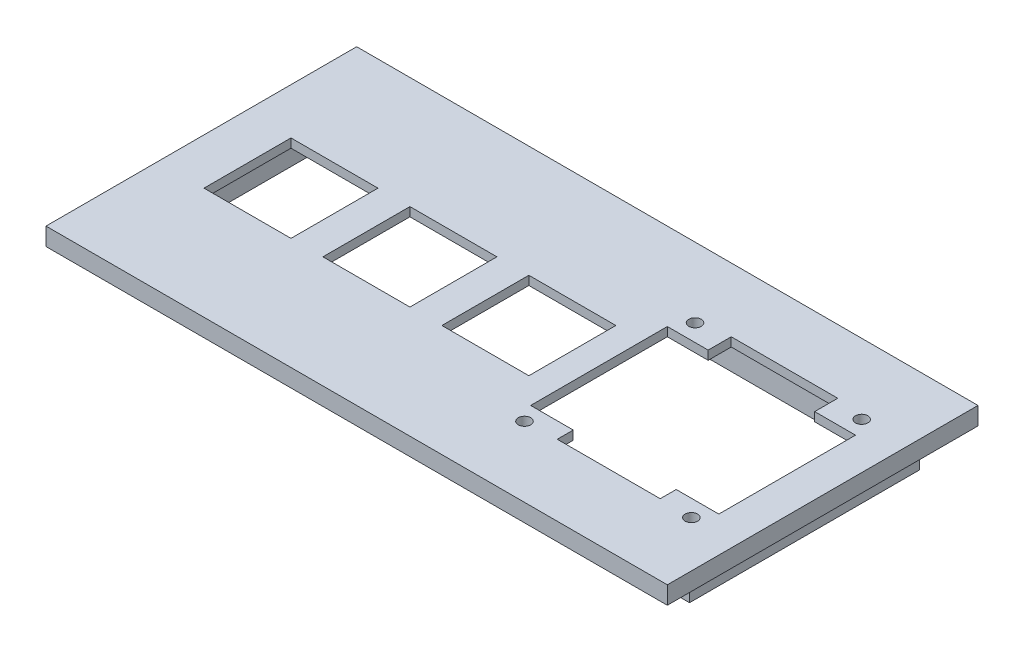
SolidWorks part; units mm, degrees
ref_plane "Front Plane" through (0, 0, 0) normal (0, 0, 1) x (1, 0, 0)
ref_plane "Top Plane" through (0, 0, 0) normal (0, 1, 0) x (1, 0, 0)
ref_plane "Right Plane" through (0, 0, 0) normal (1, 0, 0) x (0, 0, -1)
sketch "Sketch2" plane through (0, 0, 0) normal (0, 1, 0) x (1, 0, 0)
  line L1 (44.45, -22.225) -> (-44.45, -22.225)
  line L2 (44.45, -22.225) -> (44.45, 22.225)
  line L3 (44.45, 22.225) -> (-44.45, 22.225)
  line L4 (-44.45, -22.225) -> (-44.45, 22.225)
  line L5 (44.45, -22.225) -> (-44.45, 22.225) construction
  line L6 (44.45, 22.225) -> (-44.45, -22.225) construction
  point P0 (0, 0)
  dimension "D1" = 44.45
  dimension "D2" = 88.9
extrude "Boss-Extrude1" add sketch "Sketch2" along normal blind 2.54
sketch "Sketch5" plane through (0, 0, 0) normal (0, -1, 0) x (1, 0, 0)
  line L1 (41.91, -16.383) -> (-41.91, -16.383)
  line L2 (41.91, -16.383) -> (41.91, 16.51)
  line L3 (41.91, 16.51) -> (-41.91, 16.51)
  line L4 (-41.91, -16.383) -> (-41.91, 16.51)
  line L6 (-44.45, -22.225) -> (-44.45, 22.225) construction
  line L7 (44.45, 22.225) -> (44.45, -22.225) construction
  line L8 (-44.45, 22.225) -> (44.45, 22.225) construction
  line L9 (44.45, -22.225) -> (-44.45, -22.225) construction
  point P0 (0, 0)
  dimension "D1" = 2.54
  dimension "D2" = 2.54
  dimension "D3" = 5.715
  dimension "D4" = 5.842
extrude "Boss-Extrude2" add sketch "Sketch5" along normal blind 3.81
shell "Shell1" thickness 1.27 removed face at (0, -3.81, 0.0635)
sketch "Sketch3" plane through (0, 2.54, 0) normal (0, 1, 0) x (1, 0, 0)
  line L0 (-53.6471, 0) -> (105.4631, 0) construction
  line L1 (39.497, -13.868) -> (12.319, -13.868) construction
  line L2 (39.497, -13.868) -> (39.497, 13.868) construction
  line L3 (39.497, 13.868) -> (12.319, 13.868) construction
  line L4 (12.319, -13.868) -> (12.319, 13.868) construction
  line L5 (39.497, -13.868) -> (12.319, 13.868) construction
  line L6 (39.497, 13.868) -> (12.319, -13.868) construction
  line L7 (44.45, -22.225) -> (44.45, 22.225) construction
  line L8 (39.37, -9.779) -> (12.446, -9.779)
  line L9 (39.37, -9.779) -> (39.37, 9.779)
  line L10 (39.37, 9.779) -> (12.446, 9.779)
  line L11 (12.446, -9.779) -> (12.446, 9.779)
  line L12 (39.37, -9.779) -> (12.446, 9.779) construction
  line L13 (39.37, 9.779) -> (12.446, -9.779) construction
  circle A0 centre (37.846, 12.1831) radius 0.889
  circle A1 centre (13.97, 12.217) radius 0.889
  circle A2 centre (13.97, -12.1831) radius 0.889
  circle A3 centre (37.846, -12.1831) radius 0.889
  point P0 (25.908, 0)
  point P17 (25.908, 0)
  dimension "D3" = 1.778
  dimension "D4" = 1.651
  dimension "D5" = 1.651
  dimension "D6" = 1.651
  dimension "D7" = 1.6849
  dimension "D8" = 1.651
  dimension "D9" = 1.651
  dimension "D1" = 27.736
  dimension "D2" = 27.178
  dimension "D10" = 19.558
  dimension "D11" = 26.924
  dimension "D12" = 5.08
extrude "Cut-Extrude1" cut sketch "Sketch3" against normal through all both and the other way through all contours L11 L8 L9 L10 region at (25.908, 2.54, 0)
sketch "Sketch4" plane through (0, 2.54, 0) normal (0, 1, 0) x (1, 0, 0)
  line L0 (-53.9332, 0) -> (57.1003, 0) construction
  line L1 (-6.604, 21.7261) -> (-6.604, -24.0188) construction
  line L2 (8.636, -6.223) -> (-3.81, -6.223)
  line L3 (8.636, -6.223) -> (8.636, 6.223)
  line L4 (8.636, 6.223) -> (-3.81, 6.223)
  line L5 (-3.81, -6.223) -> (-3.81, 6.223)
  line L6 (8.636, -6.223) -> (-3.81, 6.223) construction
  line L7 (8.636, 6.223) -> (-3.81, -6.223) construction
  line L8 (-24.384, 21.7261) -> (-24.384, -27.2655) construction
  line L9 (12.446, 9.779) -> (12.446, -9.779) construction
  line L11 (-8.382, -6.223) -> (-20.828, -6.223)
  line L12 (-8.382, -6.223) -> (-8.382, 6.223)
  line L13 (-8.382, 6.223) -> (-20.828, 6.223)
  line L14 (-20.828, -6.223) -> (-20.828, 6.223)
  line L15 (-8.382, -6.223) -> (-20.828, 6.223) construction
  line L16 (-8.382, 6.223) -> (-20.828, -6.223) construction
  line L17 (-25.4, -6.223) -> (-37.846, -6.223)
  line L18 (-25.4, -6.223) -> (-25.4, 6.223)
  line L19 (-25.4, 6.223) -> (-37.846, 6.223)
  line L20 (-37.846, -6.223) -> (-37.846, 6.223)
  line L21 (-25.4, -6.223) -> (-37.846, 6.223) construction
  line L22 (-25.4, 6.223) -> (-37.846, -6.223) construction
  line L23 (-45.5544, -6.223) -> (13.3654, -6.223) construction
  point P3 (2.413, 0)
  point P14 (-14.605, 0)
  point P19 (-31.623, 0)
  dimension "D1" = 12.446
  dimension "D2" = 12.446
  dimension "D3" = 19.05
  dimension "D4" = 17.78
  dimension "D5" = 3.81
  dimension "D6" = 12.446
  dimension "D7" = 12.446
  dimension "D8" = 4.572
  dimension "D9" = 3.556
  dimension "D10" = 4.572
  dimension "D11" = 12.446
  dimension "D12" = 12.446
extrude "Cut-Extrude2" cut sketch "Sketch4" against normal through all both and the other way through all
extrude "Cut-Extrude3" cut sketch "Sketch3<3>" against normal blind 2.54 and the other way through all contours A3 | A2 | A1 | A0 region at (37.846, 2.54, -12.1831) region at (13.97, 2.54, -12.217) region at (13.97, 2.54, 12.1831) region at (37.846, 2.54, 12.1831)
sketch "Sketch3<3>" plane through (0, 2.54, 0) normal (0, 1, 0) x (1, 0, 0) same geometry as "Sketch3"
sketch "Sketch6" plane through (0, 2.54, 0) normal (0, 1, 0) x (1, 0, 0)
  line L0 (13.97, -12.1831) -> (37.846, -12.1831) construction
  line L1 (39.37, -9.779) -> (12.446, -9.779) construction
  line L2 (33.274, -12.065) -> (18.542, -12.065)
  line L3 (33.274, -12.065) -> (33.274, -9.779)
  line L4 (33.274, -9.779) -> (18.542, -9.779)
  line L5 (18.542, -12.065) -> (18.542, -9.779)
  line L6 (33.274, -12.065) -> (18.542, -9.779) construction
  line L7 (33.274, -9.779) -> (18.542, -12.065) construction
  line L8 (12.446, -9.779) -> (12.446, -14.5872) construction
  line L9 (39.37, -9.779) -> (39.37, -13.4425) construction
  line L10 (47.4971, 0) -> (5.9912, 0) construction
  line L11 (39.37, 9.779) -> (12.446, 9.779) construction
  line L12 (18.288, 9.779) -> (33.528, 9.779)
  line L13 (18.288, 9.779) -> (18.288, 13.081)
  line L18 (18.288, 13.081) -> (33.528, 13.081)
  line L19 (33.528, 9.779) -> (33.528, 13.081)
  line L20 (12.446, 12.4974) -> (12.446, 7.3415) construction
  line L21 (12.446, -9.779) -> (12.446, 9.779) construction
  line L22 (39.37, 13.413) -> (39.37, 8.8112) construction
  line L23 (39.37, -9.779) -> (39.37, 9.779) construction
  point P4 (25.908, -12.1831)
  dimension "D1" = 6.096
  dimension "D2" = 6.096
  dimension "D3" = 2.286
  dimension "D4" = 3.302
  dimension "D5" = 5.842
  dimension "D6" = 5.842
extrude "Cut-Extrude4" cut sketch "Sketch6" against normal blind 2.54
